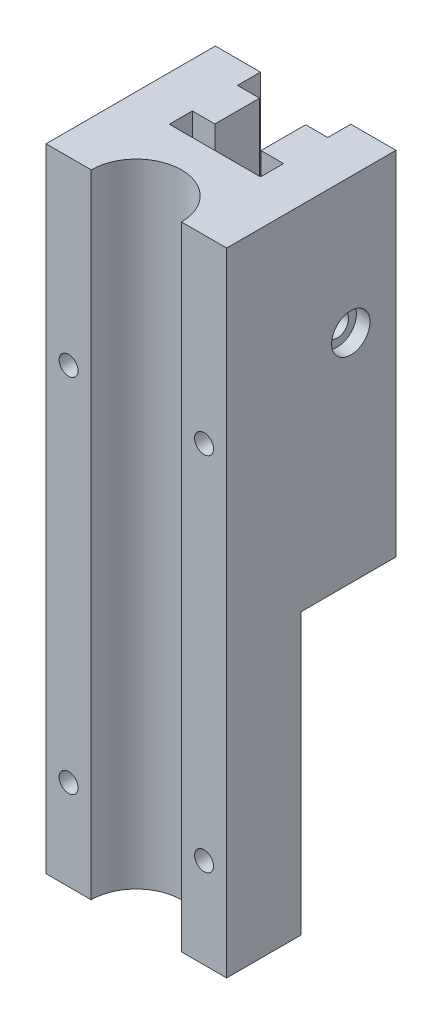
SolidWorks part; units mm, degrees
other "Markup1"
sketch "Sketch9" plane through (-20, 0, 37.5) normal (-0.6467, 0.1839, 0.7403) x (0.76, 0.0728, 0.6458)
ref_plane "Front Plane" through (0, 0, 0) normal (0, 0, 1) x (1, 0, 0)
ref_plane "Top Plane" through (0, 0, 0) normal (0, 1, 0) x (1, 0, 0)
ref_plane "Right Plane" through (0, 0, 0) normal (1, 0, 0) x (0, 0, -1)
sketch "Sketch1" plane through (0, 0, 0) normal (0, 1, 0) x (1, 0, 0)
  line L0 (10, 0) -> (-10, 0) construction
  line L1 (-10, 0) -> (-20, 0)
  line L2 (-20, 0) -> (-20, -37.5)
  line L3 (-20, -37.5) -> (20, -37.5)
  line L4 (20, -37.5) -> (20, 0)
  line L5 (20, 0) -> (10, 0)
  line L6 (10, 0) -> (10, -5.1)
  line L7 (10, -5.1) -> (5.1, -5.1)
  line L8 (5.1, -5.1) -> (5.1, -15)
  line L9 (5.1, -15) -> (10.1, -15)
  line L10 (10.1, -15) -> (10.1, -20.1)
  line L11 (10.1, -20.1) -> (-10.1, -20.1)
  line L12 (0, 0) -> (0, -20.1) construction
  line L13 (-10, 0) -> (-10, -5.1)
  line L14 (-10, -5.1) -> (-5.1, -5.1)
  line L15 (-5.1, -5.1) -> (-5.1, -15)
  line L16 (-5.1, -15) -> (-10.1, -15)
  line L17 (-10.1, -15) -> (-10.1, -20.1)
  line L18 (0, 0) -> (0, -37.5) construction
  circle A1 centre (0, -37.5) radius 10
  point P3 (0, 0)
  dimension "D10" = 20
  dimension "D1" = 37.5
  dimension "D2" = 5.1
  dimension "D3" = 4.9
  dimension "D4" = 5
  dimension "D5" = 9.9
  dimension "D6" = 5.1
  dimension "D7" = 10.1
  dimension "D8" = 40
  dimension "D9" = 20
  dimension "D11" = 37.5
extrude "Boss-Extrude1" add sketch "Sketch1" against normal blind 140 contours A1 L3 L4 L5 L6 L7 L8 L9 L10 L11 L17 L16 L15 L14 L13 L1 L2 region at (-10.5483, 0, 2.55)
sketch "Sketch5" plane through (0, -140, 0) normal (0, -1, 0) x (1, 0, 0)
  line L0 (-20, 0) -> (-20, 37.5) construction
  line L1 (20, 0) -> (-20, 0)
  line L2 (20, 0) -> (20, 21)
  line L3 (20, 21) -> (-20, 21)
  line L4 (-20, 0) -> (-20, 21)
  dimension "D1" = 21
extrude "Cut-Extrude5" cut sketch "Sketch5" against normal blind 62
sketch "Sketch3" plane through (20, 0, 0) normal (1, 0, 0) x (0, 0, -1)
  line L0 (0, -78) -> (0, 0) construction
  line L1 (0, 0) -> (-20, 0)
  line L2 (0, 0) -> (0, -25)
  line L3 (0, -25) -> (-20, -25)
  line L4 (-20, 0) -> (-20, -25)
  line L5 (-20, -25) -> (0, -25)
  line L6 (-20, -25) -> (-20, -35)
  line L7 (-20, -35) -> (0, -35)
  line L8 (0, -25) -> (0, -35)
  line L9 (-15, -25) -> (-15, -35)
  line L10 (-5, -25) -> (-5, -35)
  line L11 (-10, -25) -> (-10, -35) construction
  line L12 (-15, -30) -> (-5, -30) construction
  line L13 (-37.5, 0) -> (0, 0) construction
  circle A0 centre (-10, -30) radius 2.5
  circle A1 centre (-10, -30) radius 4.25
  dimension "D6" = 5
  dimension "D7" = 8.5
  dimension "D1" = 20
  dimension "D2" = 0
  dimension "D3" = 10
  dimension "D4" = 5
  dimension "D5" = 10
  dimension "D9" = 25
extrude "Cut-Extrude3" cut sketch "Sketch3<3>" against normal through all contours A0 region at (20, -30, 10)
sketch "Sketch3<3>" plane through (20, 0, 0) normal (1, 0, 0) x (0, 0, -1) same geometry as "Sketch3"
extrude "Cut-Extrude4" cut sketch "Sketch3" against normal blind 3 contours A1 A0 region at (20, -30, 14.1298)
sketch "Sketch7" plane through (0, 0, 37.5) normal (0, 0, 1) x (1, 0, 0)
  line L0 (-20, -140) -> (-10, -140) construction
  line L1 (-10, -140) -> (-10, 0) construction
  line L2 (10, -140) -> (20, -140) construction
  line L3 (10, -140) -> (10, 0) construction
  line L4 (20, -140) -> (20, 0) construction
  line L5 (10, 0) -> (20, 0) construction
  line L6 (-20, 0) -> (-10, 0) construction
  line L7 (-20, -140) -> (-20, 0) construction
  line L8 (-20, -140) -> (-10, -140)
  line L9 (-10, -140) -> (-10, 0)
  line L10 (10, -140) -> (20, -140)
  line L11 (10, -140) -> (10, 0)
  line L12 (20, -140) -> (20, 0)
  line L13 (10, 0) -> (20, 0)
  line L14 (-20, 0) -> (-10, 0)
  line L15 (-20, -140) -> (-20, 0)
  line L16 (0, -140) -> (0, 0) construction
  line L17 (-10, 0) -> (10, 0)
  line L18 (-10, 0) -> (-10, -140)
  line L19 (-10, -140) -> (10, -140)
  line L20 (10, 0) -> (10, -140)
  line L21 (-15, 0) -> (-15, -140) construction
  line L22 (15, 0) -> (15, -140) construction
  circle A0 centre (-15, -120) radius 2.1
  circle A1 centre (15, -120) radius 2.1
  circle A2 centre (-15, -40) radius 2.1
  circle A3 centre (15, -40) radius 2.1
  dimension "D1" = 4.2
  dimension "D2" = 4.2
  dimension "D7" = 4.2
  dimension "D8" = 4.2
  dimension "D3" = 20
  dimension "D4" = 20
  dimension "D5" = 40
  dimension "D6" = 40
extrude "Cut-Extrude7" cut sketch "Sketch7" against normal blind 10 contours A2 | A3 | A1 | A0
sketch "Sketch10" plane through (-20, 0, 0) normal (-1, 0, 0) x (0, 0, 1)
  line L1 (13.4995, -29.9388) -> (11.6967, -26.9388)
  line L2 (11.6967, -26.9388) -> (8.1972, -27)
  line L3 (8.1972, -27) -> (6.5005, -30.0612)
  line L4 (6.5005, -30.0612) -> (8.3033, -33.0612)
  line L5 (8.3033, -33.0612) -> (11.8028, -33)
  line L6 (11.8028, -33) -> (13.4995, -29.9388)
  circle A0 centre (10, -30) radius 2.5 construction
  circle A1 centre (10, -30) radius 2.5
  circle A2 centre (10, -30) radius 3.0311 construction
  point P3 (0, 0)
  point P12 (6.9696, -29.9346)
  dimension "D1" = 3.5
  dimension "D2" = 3
extrude "Cut-Extrude8" cut sketch "Sketch10" against normal blind 3
